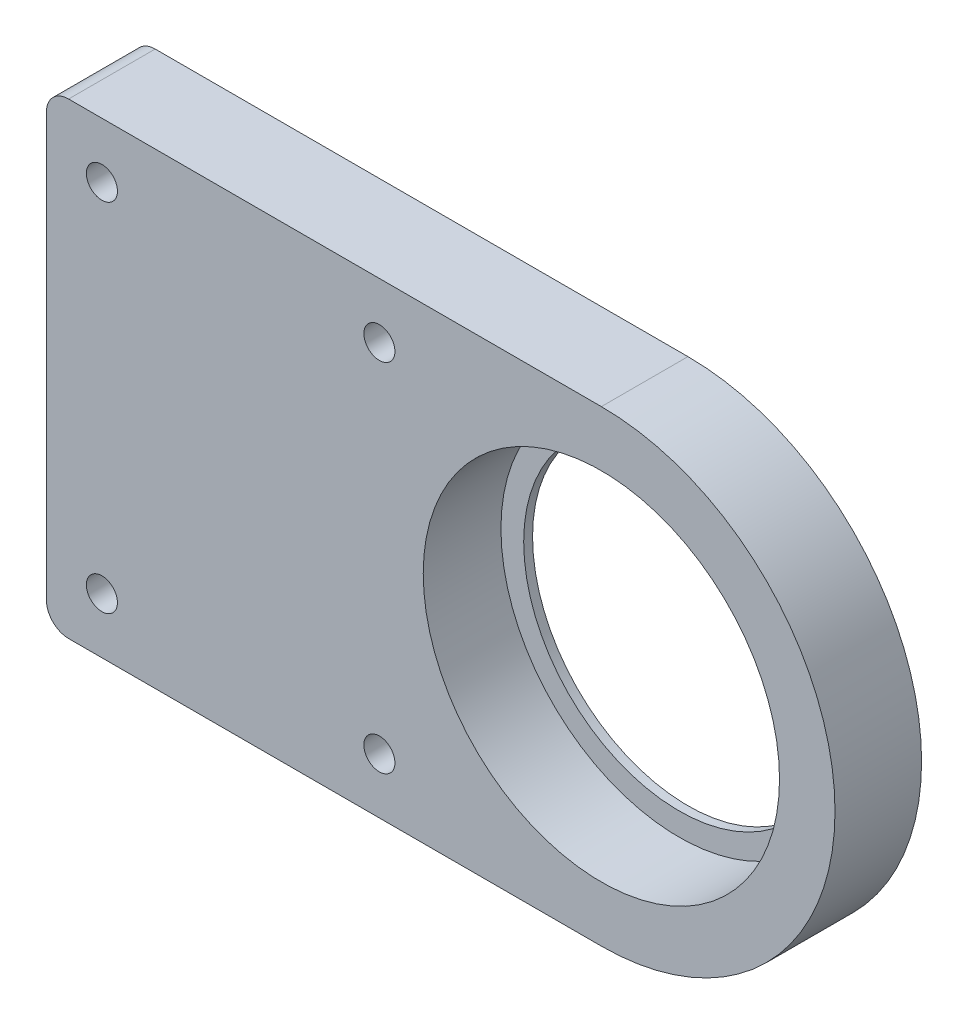
SolidWorks part; units mm, degrees
ref_plane "Front Plane" through (0, 0, 0) normal (0, 0, 1) x (1, 0, 0)
ref_plane "Top Plane" through (0, 0, 0) normal (0, 1, 0) x (1, 0, 0)
ref_plane "Right Plane" through (0, 0, 0) normal (1, 0, 0) x (0, 0, -1)
sketch "Sketch1" plane through (0, 0, 0) normal (0, 0, 1) x (1, 0, 0)
  line L0 (0, 21.05) -> (-50, 21.05)
  line L5 (0, -21.05) -> (-50, -21.05)
  line L6 (-50, -21.05) -> (-50, 21.05)
  circle A0 centre (0, 0) radius 16.05
  arc A1 (0, -21.05) -> (0, 21.05) centre (0, 0) ccw
  dimension "D1" = 32.1
  dimension "D2" = 50
  dimension "D3" = 5
extrude "Boss-Extrude1" add sketch "Sketch1" along normal blind 3.5 and the other way blind 3.5
sketch "Sketch2" plane through (0, 0, -3.5) normal (0, 0, -1) x (-1, 0, 0)
  line L3 (0, -21.05) -> (50, -21.05)
  line L4 (50, -21.05) -> (50, 21.05)
  line L5 (50, 21.05) -> (0, 21.05)
  line L6 (0, -21.05) -> (50, -21.05)
  line L7 (50, -21.05) -> (50, 21.05)
  line L8 (50, 21.05) -> (0, 21.05)
  circle A0 centre (0, 0) radius 14
  arc A3 (0, 21.05) -> (0, -21.05) centre (0, 0) ccw
  arc A4 (0, 21.05) -> (0, -21.05) centre (0, 0) ccw
  dimension "D1" = 0
  dimension "D2" = 28
extrude "Boss-Extrude2" add sketch "Sketch2" along normal blind 0.8
sketch "Sketch3" plane through (0, 0, -4.3) normal (0, 0, -1) x (-1, 0, 0)
  line L2 (50, -21.05) -> (50, 21.05) construction
  line L3 (20, 16.05) -> (45, 16.05) construction
  line L4 (20, 16.05) -> (20, -16.05) construction
  line L5 (20, -16.05) -> (45, -16.05) construction
  line L6 (45, 16.05) -> (45, -16.05) construction
  line L7 (50, 21.05) -> (0, 21.05) construction
  line L8 (0, -21.05) -> (50, -21.05) construction
  circle A1 centre (20, 16.05) radius 1.4
  circle A2 centre (45, 16.05) radius 1.4
  circle A3 centre (45, -16.05) radius 1.4
  circle A4 centre (20, -16.05) radius 1.4
  dimension "D1" = 5
  dimension "D2" = 5
  dimension "D3" = 5
  dimension "D4" = 25
extrude "Cut-Extrude1" cut sketch "Sketch3" against normal through all
fillet "Fillet1" radius 2 2 edges at (-50, -21.05, -0.4) (-50, 21.05, -0.4)
